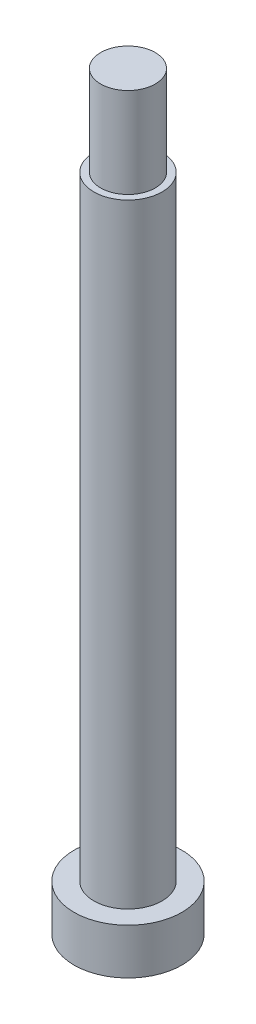
SolidWorks part; units mm, degrees
ref_plane "前视基准面" through (0, 0, 0) normal (0, 0, 1) x (1, 0, 0)
ref_plane "上视基准面" through (0, 0, 0) normal (0, 1, 0) x (1, 0, 0)
ref_plane "右视基准面" through (0, 0, 0) normal (1, 0, 0) x (0, 0, -1)
other "Configuration Table"
sketch "草图1" plane through (0, 0, 0) normal (0, 1, 0) x (1, 0, 0)
  circle A0 centre (0, 0) radius 5
  circle A1 centre (0, 0) radius 7.9
  circle A2 centre (0, 0) radius 4
  dimension "D1" = 8
  dimension "D2" = 10
  dimension "D3" = 15.8
extrude "凸台-拉伸1" add sketch "草图1" along normal blind 109.9 contours A2 region at (0, 0, 0)
extrude "凸台-拉伸2" add sketch "草图1<3>" along normal blind 96.7 contours A0 A2 region at (-4.8586, 0, 0)
sketch "草图1<3>" plane through (0, 0, 0) normal (0, 1, 0) x (1, 0, 0) same geometry as "草图1"
extrude "凸台-拉伸3" add sketch "草图1<4>" along normal blind 6.7 contours A1 A0 region at (-7.6766, 0, 0)
sketch "草图1<4>" plane through (0, 0, 0) normal (0, 1, 0) x (1, 0, 0) same geometry as "草图1"
sketch "草图2" plane through (0, 0, 0) normal (0, -1, 0) x (1, 0, 0)
  line L1 (2.5, 1.4434) -> (0, 2.8868)
  line L2 (0, 2.8868) -> (-2.5, 1.4434)
  line L3 (-2.5, 1.4434) -> (-2.5, -1.4434)
  line L4 (-2.5, -1.4434) -> (0, -2.8868)
  line L5 (0, -2.8868) -> (2.5, -1.4434)
  line L6 (2.5, -1.4434) -> (2.5, 1.4434)
  circle A0 centre (0, 0) radius 2.5 construction
  dimension "D1" = 5
extrude "切除-拉伸1" cut sketch "草图2" against normal blind 3
